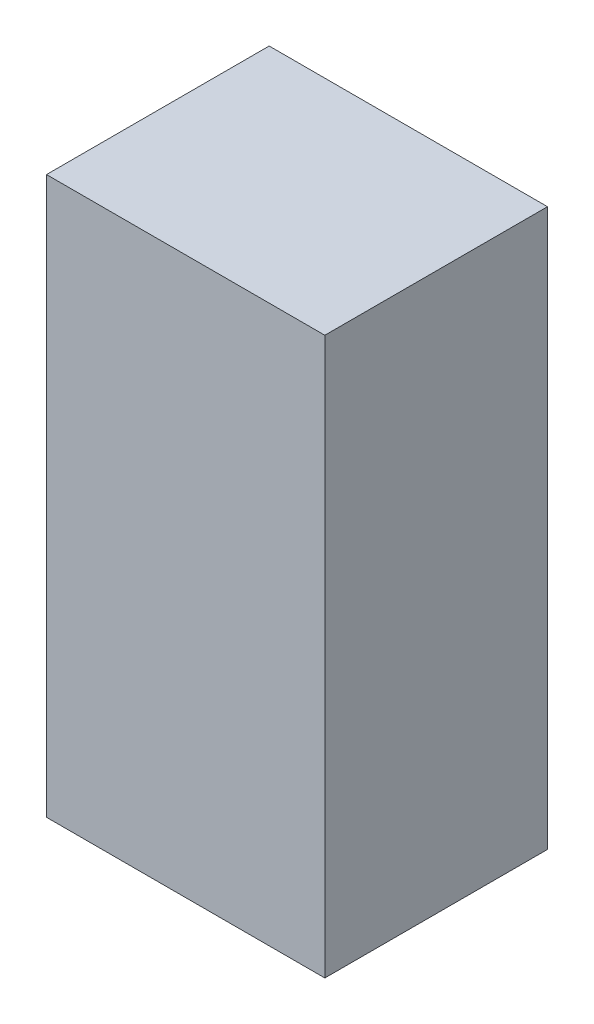
SolidWorks part; units mm, degrees
ref_plane "Front Plane" through (0, 0, 0) normal (0, 0, 1) x (1, 0, 0)
ref_plane "Top Plane" through (0, 0, 0) normal (0, 1, 0) x (1, 0, 0)
ref_plane "Right Plane" through (0, 0, 0) normal (1, 0, 0) x (0, 0, -1)
sketch "Sketch1" plane through (0, 0, 0) normal (0, 1, 0) x (1, 0, 0)
  line L1 (-25, 20) -> (25, 20)
  line L2 (-25, 20) -> (-25, -20)
  line L3 (-25, -20) -> (25, -20)
  line L4 (25, 20) -> (25, -20)
  line L5 (-25, 20) -> (25, -20) construction
  line L6 (-25, -20) -> (25, 20) construction
  point P0 (0, 0)
  dimension "D1" = 50
  dimension "D2" = 40
extrude "Boss-Extrude1" add sketch "Sketch1" along normal blind 100
ref_axis "Axis1" through (0, 210, 0) along (0, -1, 0)
